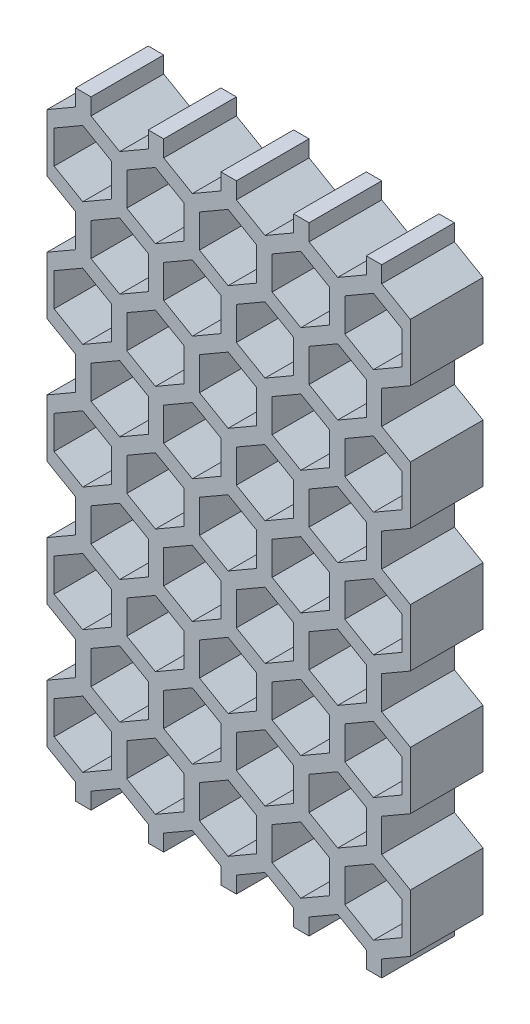
SolidWorks part; units mm, degrees
ref_plane "Front Plane" through (0, 0, 0) normal (0, 0, 1) x (1, 0, 0)
ref_plane "Top Plane" through (0, 0, 0) normal (0, 1, 0) x (1, 0, 0)
ref_plane "Right Plane" through (0, 0, 0) normal (1, 0, 0) x (0, 0, -1)
sketch "Sketch1" plane through (0, 0, 0) normal (0, 0, 1) x (1, 0, 0)
  line L0 (1.25, -1.0104) -> (0.25, -1.5877)
  line L1 (0, 1.1547) -> (-1, 0.5774)
  line L2 (-1, 0.5774) -> (-1, -0.5774)
  line L3 (-1, -0.5774) -> (0, -1.1547)
  line L4 (0, -1.1547) -> (1, -0.5774)
  line L5 (1, -0.5774) -> (1, 0.5774)
  line L6 (1, 0.5774) -> (0, 1.1547)
  line L7 (0.25, -1.5877) -> (0.25, -2.7424)
  line L8 (0.25, -2.7424) -> (1.25, -3.3198)
  line L9 (1.25, -3.3198) -> (2.25, -2.7424)
  line L10 (2.25, -2.7424) -> (2.25, -1.5877)
  line L11 (2.25, -1.5877) -> (1.25, -1.0104)
  line L12 (3.79, -1.0104) -> (2.79, -1.5877)
  line L13 (2.54, 1.1547) -> (1.54, 0.5774)
  line L14 (1.54, 0.5774) -> (1.54, -0.5774)
  line L15 (1.54, -0.5774) -> (2.54, -1.1547)
  line L16 (2.54, -1.1547) -> (3.54, -0.5774)
  line L17 (3.54, -0.5774) -> (3.54, 0.5774)
  line L18 (3.54, 0.5774) -> (2.54, 1.1547)
  line L19 (2.79, -1.5877) -> (2.79, -2.7424)
  line L20 (2.79, -2.7424) -> (3.79, -3.3198)
  line L21 (3.79, -3.3198) -> (4.79, -2.7424)
  line L22 (4.79, -2.7424) -> (4.79, -1.5877)
  line L23 (4.79, -1.5877) -> (3.79, -1.0104)
  line L24 (6.33, -1.0104) -> (5.33, -1.5877)
  line L25 (5.08, 1.1547) -> (4.08, 0.5774)
  line L26 (4.08, 0.5774) -> (4.08, -0.5774)
  line L27 (4.08, -0.5774) -> (5.08, -1.1547)
  line L28 (5.08, -1.1547) -> (6.08, -0.5774)
  line L29 (6.08, -0.5774) -> (6.08, 0.5774)
  line L30 (6.08, 0.5774) -> (5.08, 1.1547)
  line L31 (5.33, -1.5877) -> (5.33, -2.7424)
  line L32 (5.33, -2.7424) -> (6.33, -3.3198)
  line L33 (6.33, -3.3198) -> (7.33, -2.7424)
  line L34 (7.33, -2.7424) -> (7.33, -1.5877)
  line L35 (7.33, -1.5877) -> (6.33, -1.0104)
  line L36 (8.87, -1.0104) -> (7.87, -1.5877)
  line L37 (7.62, 1.1547) -> (6.62, 0.5774)
  line L38 (6.62, 0.5774) -> (6.62, -0.5774)
  line L39 (6.62, -0.5774) -> (7.62, -1.1547)
  line L40 (7.62, -1.1547) -> (8.62, -0.5774)
  line L41 (8.62, -0.5774) -> (8.62, 0.5774)
  line L42 (8.62, 0.5774) -> (7.62, 1.1547)
  line L43 (7.87, -1.5877) -> (7.87, -2.7424)
  line L44 (7.87, -2.7424) -> (8.87, -3.3198)
  line L45 (8.87, -3.3198) -> (9.87, -2.7424)
  line L46 (9.87, -2.7424) -> (9.87, -1.5877)
  line L47 (9.87, -1.5877) -> (8.87, -1.0104)
  line L48 (11.41, -1.0104) -> (10.41, -1.5877)
  line L49 (10.16, 1.1547) -> (9.16, 0.5774)
  line L50 (9.16, 0.5774) -> (9.16, -0.5774)
  line L51 (9.16, -0.5774) -> (10.16, -1.1547)
  line L52 (10.16, -1.1547) -> (11.16, -0.5774)
  line L53 (11.16, -0.5774) -> (11.16, 0.5774)
  line L54 (11.16, 0.5774) -> (10.16, 1.1547)
  line L55 (10.41, -1.5877) -> (10.41, -2.7424)
  line L56 (10.41, -2.7424) -> (11.41, -3.3198)
  line L57 (11.41, -3.3198) -> (12.41, -2.7424)
  line L58 (12.41, -2.7424) -> (12.41, -1.5877)
  line L59 (12.41, -1.5877) -> (11.41, -1.0104)
  line L60 (13.95, -1.0104) -> (12.95, -1.5877)
  line L61 (12.7, 1.1547) -> (11.7, 0.5774)
  line L62 (11.7, 0.5774) -> (11.7, -0.5774)
  line L63 (11.7, -0.5774) -> (12.7, -1.1547)
  line L64 (12.7, -1.1547) -> (13.7, -0.5774)
  line L65 (13.7, -0.5774) -> (13.7, 0.5774)
  line L66 (13.7, 0.5774) -> (12.7, 1.1547)
  line L67 (12.95, -1.5877) -> (12.95, -2.7424)
  line L68 (12.95, -2.7424) -> (13.95, -3.3198)
  line L69 (13.95, -3.3198) -> (14.95, -2.7424)
  line L70 (14.95, -2.7424) -> (14.95, -1.5877)
  line L71 (14.95, -1.5877) -> (13.95, -1.0104)
  line L72 (3.79, -5.3284) -> (2.79, -5.9057)
  line L73 (2.54, -3.1633) -> (1.54, -3.7406)
  line L74 (1.54, -3.7406) -> (1.54, -4.8954)
  line L75 (1.54, -4.8954) -> (2.54, -5.4727)
  line L76 (2.54, -5.4727) -> (3.54, -4.8954)
  line L77 (3.54, -4.8954) -> (3.54, -3.7406)
  line L78 (3.54, -3.7406) -> (2.54, -3.1633)
  line L79 (2.79, -5.9057) -> (2.79, -7.0604)
  line L80 (2.79, -7.0604) -> (3.79, -7.6378)
  line L81 (3.79, -7.6378) -> (4.79, -7.0604)
  line L82 (4.79, -7.0604) -> (4.79, -5.9057)
  line L83 (4.79, -5.9057) -> (3.79, -5.3284)
  line L84 (6.33, -5.3284) -> (5.33, -5.9057)
  line L85 (5.08, -3.1633) -> (4.08, -3.7406)
  line L86 (4.08, -3.7406) -> (4.08, -4.8954)
  line L87 (4.08, -4.8954) -> (5.08, -5.4727)
  line L88 (5.08, -5.4727) -> (6.08, -4.8954)
  line L89 (6.08, -4.8954) -> (6.08, -3.7406)
  line L90 (6.08, -3.7406) -> (5.08, -3.1633)
  line L91 (5.33, -5.9057) -> (5.33, -7.0604)
  line L92 (5.33, -7.0604) -> (6.33, -7.6378)
  line L93 (6.33, -7.6378) -> (7.33, -7.0604)
  line L94 (7.33, -7.0604) -> (7.33, -5.9057)
  line L95 (7.33, -5.9057) -> (6.33, -5.3284)
  line L96 (8.87, -5.3284) -> (7.87, -5.9057)
  line L97 (7.62, -3.1633) -> (6.62, -3.7406)
  line L98 (6.62, -3.7406) -> (6.62, -4.8954)
  line L99 (6.62, -4.8954) -> (7.62, -5.4727)
  line L100 (7.62, -5.4727) -> (8.62, -4.8954)
  line L101 (8.62, -4.8954) -> (8.62, -3.7406)
  line L102 (8.62, -3.7406) -> (7.62, -3.1633)
  line L103 (7.87, -5.9057) -> (7.87, -7.0604)
  line L104 (7.87, -7.0604) -> (8.87, -7.6378)
  line L105 (8.87, -7.6378) -> (9.87, -7.0604)
  line L106 (9.87, -7.0604) -> (9.87, -5.9057)
  line L107 (9.87, -5.9057) -> (8.87, -5.3284)
  line L108 (11.41, -5.3284) -> (10.41, -5.9057)
  line L109 (10.16, -3.1633) -> (9.16, -3.7406)
  line L110 (9.16, -3.7406) -> (9.16, -4.8954)
  line L111 (9.16, -4.8954) -> (10.16, -5.4727)
  line L112 (10.16, -5.4727) -> (11.16, -4.8954)
  line L113 (11.16, -4.8954) -> (11.16, -3.7406)
  line L114 (11.16, -3.7406) -> (10.16, -3.1633)
  line L115 (10.41, -5.9057) -> (10.41, -7.0604)
  line L116 (10.41, -7.0604) -> (11.41, -7.6378)
  line L117 (11.41, -7.6378) -> (12.41, -7.0604)
  line L118 (12.41, -7.0604) -> (12.41, -5.9057)
  line L119 (12.41, -5.9057) -> (11.41, -5.3284)
  line L120 (13.95, -5.3284) -> (12.95, -5.9057)
  line L121 (12.7, -3.1633) -> (11.7, -3.7406)
  line L122 (11.7, -3.7406) -> (11.7, -4.8954)
  line L123 (11.7, -4.8954) -> (12.7, -5.4727)
  line L124 (12.7, -5.4727) -> (13.7, -4.8954)
  line L125 (13.7, -4.8954) -> (13.7, -3.7406)
  line L126 (13.7, -3.7406) -> (12.7, -3.1633)
  line L127 (12.95, -5.9057) -> (12.95, -7.0604)
  line L128 (12.95, -7.0604) -> (13.95, -7.6378)
  line L129 (13.95, -7.6378) -> (14.95, -7.0604)
  line L130 (14.95, -7.0604) -> (14.95, -5.9057)
  line L131 (14.95, -5.9057) -> (13.95, -5.3284)
  line L132 (3.79, -9.6464) -> (2.79, -10.2237)
  line L133 (2.54, -7.4813) -> (1.54, -8.0586)
  line L134 (1.54, -8.0586) -> (1.54, -9.2134)
  line L135 (1.54, -9.2134) -> (2.54, -9.7907)
  line L136 (2.54, -9.7907) -> (3.54, -9.2134)
  line L137 (3.54, -9.2134) -> (3.54, -8.0586)
  line L138 (3.54, -8.0586) -> (2.54, -7.4813)
  line L139 (2.79, -10.2237) -> (2.79, -11.3784)
  line L140 (2.79, -11.3784) -> (3.79, -11.9558)
  line L141 (3.79, -11.9558) -> (4.79, -11.3784)
  line L142 (4.79, -11.3784) -> (4.79, -10.2237)
  line L143 (4.79, -10.2237) -> (3.79, -9.6464)
  line L144 (6.33, -9.6464) -> (5.33, -10.2237)
  line L145 (5.08, -7.4813) -> (4.08, -8.0586)
  line L146 (4.08, -8.0586) -> (4.08, -9.2134)
  line L147 (4.08, -9.2134) -> (5.08, -9.7907)
  line L148 (5.08, -9.7907) -> (6.08, -9.2134)
  line L149 (6.08, -9.2134) -> (6.08, -8.0586)
  line L150 (6.08, -8.0586) -> (5.08, -7.4813)
  line L151 (5.33, -10.2237) -> (5.33, -11.3784)
  line L152 (5.33, -11.3784) -> (6.33, -11.9558)
  line L153 (6.33, -11.9558) -> (7.33, -11.3784)
  line L154 (7.33, -11.3784) -> (7.33, -10.2237)
  line L155 (7.33, -10.2237) -> (6.33, -9.6464)
  line L156 (8.87, -9.6464) -> (7.87, -10.2237)
  line L157 (7.62, -7.4813) -> (6.62, -8.0586)
  line L158 (6.62, -8.0586) -> (6.62, -9.2134)
  line L159 (6.62, -9.2134) -> (7.62, -9.7907)
  line L160 (7.62, -9.7907) -> (8.62, -9.2134)
  line L161 (8.62, -9.2134) -> (8.62, -8.0586)
  line L162 (8.62, -8.0586) -> (7.62, -7.4813)
  line L163 (7.87, -10.2237) -> (7.87, -11.3784)
  line L164 (7.87, -11.3784) -> (8.87, -11.9558)
  line L165 (8.87, -11.9558) -> (9.87, -11.3784)
  line L166 (9.87, -11.3784) -> (9.87, -10.2237)
  line L167 (9.87, -10.2237) -> (8.87, -9.6464)
  line L168 (11.41, -9.6464) -> (10.41, -10.2237)
  line L169 (10.16, -7.4813) -> (9.16, -8.0586)
  line L170 (9.16, -8.0586) -> (9.16, -9.2134)
  line L171 (9.16, -9.2134) -> (10.16, -9.7907)
  line L172 (10.16, -9.7907) -> (11.16, -9.2134)
  line L173 (11.16, -9.2134) -> (11.16, -8.0586)
  line L174 (11.16, -8.0586) -> (10.16, -7.4813)
  line L175 (10.41, -10.2237) -> (10.41, -11.3784)
  line L176 (10.41, -11.3784) -> (11.41, -11.9558)
  line L177 (11.41, -11.9558) -> (12.41, -11.3784)
  line L178 (12.41, -11.3784) -> (12.41, -10.2237)
  line L179 (12.41, -10.2237) -> (11.41, -9.6464)
  line L180 (13.95, -9.6464) -> (12.95, -10.2237)
  line L181 (12.7, -7.4813) -> (11.7, -8.0586)
  line L182 (11.7, -8.0586) -> (11.7, -9.2134)
  line L183 (11.7, -9.2134) -> (12.7, -9.7907)
  line L184 (12.7, -9.7907) -> (13.7, -9.2134)
  line L185 (13.7, -9.2134) -> (13.7, -8.0586)
  line L186 (13.7, -8.0586) -> (12.7, -7.4813)
  line L187 (12.95, -10.2237) -> (12.95, -11.3784)
  line L188 (12.95, -11.3784) -> (13.95, -11.9558)
  line L189 (13.95, -11.9558) -> (14.95, -11.3784)
  line L190 (14.95, -11.3784) -> (14.95, -10.2237)
  line L191 (14.95, -10.2237) -> (13.95, -9.6464)
  line L192 (3.79, -13.9644) -> (2.79, -14.5417)
  line L193 (2.54, -11.7993) -> (1.54, -12.3766)
  line L194 (1.54, -12.3766) -> (1.54, -13.5314)
  line L195 (1.54, -13.5314) -> (2.54, -14.1087)
  line L196 (2.54, -14.1087) -> (3.54, -13.5314)
  line L197 (3.54, -13.5314) -> (3.54, -12.3766)
  line L198 (3.54, -12.3766) -> (2.54, -11.7993)
  line L199 (2.79, -14.5417) -> (2.79, -15.6964)
  line L200 (2.79, -15.6964) -> (3.79, -16.2738)
  line L201 (3.79, -16.2738) -> (4.79, -15.6964)
  line L202 (4.79, -15.6964) -> (4.79, -14.5417)
  line L203 (4.79, -14.5417) -> (3.79, -13.9644)
  line L204 (6.33, -13.9644) -> (5.33, -14.5417)
  line L205 (5.08, -11.7993) -> (4.08, -12.3766)
  line L206 (4.08, -12.3766) -> (4.08, -13.5314)
  line L207 (4.08, -13.5314) -> (5.08, -14.1087)
  line L208 (5.08, -14.1087) -> (6.08, -13.5314)
  line L209 (6.08, -13.5314) -> (6.08, -12.3766)
  line L210 (6.08, -12.3766) -> (5.08, -11.7993)
  line L211 (5.33, -14.5417) -> (5.33, -15.6964)
  line L212 (5.33, -15.6964) -> (6.33, -16.2738)
  line L213 (6.33, -16.2738) -> (7.33, -15.6964)
  line L214 (7.33, -15.6964) -> (7.33, -14.5417)
  line L215 (7.33, -14.5417) -> (6.33, -13.9644)
  line L216 (8.87, -13.9644) -> (7.87, -14.5417)
  line L217 (7.62, -11.7993) -> (6.62, -12.3766)
  line L218 (6.62, -12.3766) -> (6.62, -13.5314)
  line L219 (6.62, -13.5314) -> (7.62, -14.1087)
  line L220 (7.62, -14.1087) -> (8.62, -13.5314)
  line L221 (8.62, -13.5314) -> (8.62, -12.3766)
  line L222 (8.62, -12.3766) -> (7.62, -11.7993)
  line L223 (7.87, -14.5417) -> (7.87, -15.6964)
  line L224 (7.87, -15.6964) -> (8.87, -16.2738)
  line L225 (8.87, -16.2738) -> (9.87, -15.6964)
  line L226 (9.87, -15.6964) -> (9.87, -14.5417)
  line L227 (9.87, -14.5417) -> (8.87, -13.9644)
  line L228 (11.41, -13.9644) -> (10.41, -14.5417)
  line L229 (10.16, -11.7993) -> (9.16, -12.3766)
  line L230 (9.16, -12.3766) -> (9.16, -13.5314)
  line L231 (9.16, -13.5314) -> (10.16, -14.1087)
  line L232 (10.16, -14.1087) -> (11.16, -13.5314)
  line L233 (11.16, -13.5314) -> (11.16, -12.3766)
  line L234 (11.16, -12.3766) -> (10.16, -11.7993)
  line L235 (10.41, -14.5417) -> (10.41, -15.6964)
  line L236 (10.41, -15.6964) -> (11.41, -16.2738)
  line L237 (11.41, -16.2738) -> (12.41, -15.6964)
  line L238 (12.41, -15.6964) -> (12.41, -14.5417)
  line L239 (12.41, -14.5417) -> (11.41, -13.9644)
  line L240 (13.95, -13.9644) -> (12.95, -14.5417)
  line L241 (12.7, -11.7993) -> (11.7, -12.3766)
  line L242 (11.7, -12.3766) -> (11.7, -13.5314)
  line L243 (11.7, -13.5314) -> (12.7, -14.1087)
  line L244 (12.7, -14.1087) -> (13.7, -13.5314)
  line L245 (13.7, -13.5314) -> (13.7, -12.3766)
  line L246 (13.7, -12.3766) -> (12.7, -11.7993)
  line L247 (12.95, -14.5417) -> (12.95, -15.6964)
  line L248 (12.95, -15.6964) -> (13.95, -16.2738)
  line L249 (13.95, -16.2738) -> (14.95, -15.6964)
  line L250 (14.95, -15.6964) -> (14.95, -14.5417)
  line L251 (14.95, -14.5417) -> (13.95, -13.9644)
  line L252 (3.79, -18.2824) -> (2.79, -18.8597)
  line L253 (2.54, -16.1173) -> (1.54, -16.6946)
  line L254 (1.54, -16.6946) -> (1.54, -17.8494)
  line L255 (1.54, -17.8494) -> (2.54, -18.4267)
  line L256 (2.54, -18.4267) -> (3.54, -17.8494)
  line L257 (3.54, -17.8494) -> (3.54, -16.6946)
  line L258 (3.54, -16.6946) -> (2.54, -16.1173)
  line L259 (2.79, -18.8597) -> (2.79, -20.0144)
  line L260 (2.79, -20.0144) -> (3.79, -20.5918)
  line L261 (3.79, -20.5918) -> (4.79, -20.0144)
  line L262 (4.79, -20.0144) -> (4.79, -18.8597)
  line L263 (4.79, -18.8597) -> (3.79, -18.2824)
  line L264 (6.33, -18.2824) -> (5.33, -18.8597)
  line L265 (5.08, -16.1173) -> (4.08, -16.6946)
  line L266 (4.08, -16.6946) -> (4.08, -17.8494)
  line L267 (4.08, -17.8494) -> (5.08, -18.4267)
  line L268 (5.08, -18.4267) -> (6.08, -17.8494)
  line L269 (6.08, -17.8494) -> (6.08, -16.6946)
  line L270 (6.08, -16.6946) -> (5.08, -16.1173)
  line L271 (5.33, -18.8597) -> (5.33, -20.0144)
  line L272 (5.33, -20.0144) -> (6.33, -20.5918)
  line L273 (6.33, -20.5918) -> (7.33, -20.0144)
  line L274 (7.33, -20.0144) -> (7.33, -18.8597)
  line L275 (7.33, -18.8597) -> (6.33, -18.2824)
  line L276 (8.87, -18.2824) -> (7.87, -18.8597)
  line L277 (7.62, -16.1173) -> (6.62, -16.6946)
  line L278 (6.62, -16.6946) -> (6.62, -17.8494)
  line L279 (6.62, -17.8494) -> (7.62, -18.4267)
  line L280 (7.62, -18.4267) -> (8.62, -17.8494)
  line L281 (8.62, -17.8494) -> (8.62, -16.6946)
  line L282 (8.62, -16.6946) -> (7.62, -16.1173)
  line L283 (7.87, -18.8597) -> (7.87, -20.0144)
  line L284 (7.87, -20.0144) -> (8.87, -20.5918)
  line L285 (8.87, -20.5918) -> (9.87, -20.0144)
  line L286 (9.87, -20.0144) -> (9.87, -18.8597)
  line L287 (9.87, -18.8597) -> (8.87, -18.2824)
  line L288 (11.41, -18.2824) -> (10.41, -18.8597)
  line L289 (10.16, -16.1173) -> (9.16, -16.6946)
  line L290 (9.16, -16.6946) -> (9.16, -17.8494)
  line L291 (9.16, -17.8494) -> (10.16, -18.4267)
  line L292 (10.16, -18.4267) -> (11.16, -17.8494)
  line L293 (11.16, -17.8494) -> (11.16, -16.6946)
  line L294 (11.16, -16.6946) -> (10.16, -16.1173)
  line L295 (10.41, -18.8597) -> (10.41, -20.0144)
  line L296 (10.41, -20.0144) -> (11.41, -20.5918)
  line L297 (11.41, -20.5918) -> (12.41, -20.0144)
  line L298 (12.41, -20.0144) -> (12.41, -18.8597)
  line L299 (12.41, -18.8597) -> (11.41, -18.2824)
  line L300 (13.95, -18.2824) -> (12.95, -18.8597)
  line L301 (12.7, -16.1173) -> (11.7, -16.6946)
  line L302 (11.7, -16.6946) -> (11.7, -17.8494)
  line L303 (11.7, -17.8494) -> (12.7, -18.4267)
  line L304 (12.7, -18.4267) -> (13.7, -17.8494)
  line L305 (13.7, -17.8494) -> (13.7, -16.6946)
  line L306 (13.7, -16.6946) -> (12.7, -16.1173)
  line L307 (12.95, -18.8597) -> (12.95, -20.0144)
  line L308 (12.95, -20.0144) -> (13.95, -20.5918)
  line L309 (13.95, -20.5918) -> (14.95, -20.0144)
  line L310 (14.95, -20.0144) -> (14.95, -18.8597)
  line L311 (14.95, -18.8597) -> (13.95, -18.2824)
  line L312 (3.79, -22.6004) -> (2.79, -23.1777)
  line L313 (2.54, -20.4353) -> (1.54, -21.0126)
  line L314 (1.54, -21.0126) -> (1.54, -22.1674)
  line L315 (1.54, -22.1674) -> (2.54, -22.7447)
  line L316 (2.54, -22.7447) -> (3.54, -22.1674)
  line L317 (3.54, -22.1674) -> (3.54, -21.0126)
  line L318 (3.54, -21.0126) -> (2.54, -20.4353)
  line L319 (2.79, -23.1777) -> (2.79, -24.3324)
  line L320 (2.79, -24.3324) -> (3.79, -24.9098)
  line L321 (3.79, -24.9098) -> (4.79, -24.3324)
  line L322 (4.79, -24.3324) -> (4.79, -23.1777)
  line L323 (4.79, -23.1777) -> (3.79, -22.6004)
  line L324 (6.33, -22.6004) -> (5.33, -23.1777)
  line L325 (5.08, -20.4353) -> (4.08, -21.0126)
  line L326 (4.08, -21.0126) -> (4.08, -22.1674)
  line L327 (4.08, -22.1674) -> (5.08, -22.7447)
  line L328 (5.08, -22.7447) -> (6.08, -22.1674)
  line L329 (6.08, -22.1674) -> (6.08, -21.0126)
  line L330 (6.08, -21.0126) -> (5.08, -20.4353)
  line L331 (5.33, -23.1777) -> (5.33, -24.3324)
  line L332 (5.33, -24.3324) -> (6.33, -24.9098)
  line L333 (6.33, -24.9098) -> (7.33, -24.3324)
  line L334 (7.33, -24.3324) -> (7.33, -23.1777)
  line L335 (7.33, -23.1777) -> (6.33, -22.6004)
  line L336 (8.87, -22.6004) -> (7.87, -23.1777)
  line L337 (7.62, -20.4353) -> (6.62, -21.0126)
  line L338 (6.62, -21.0126) -> (6.62, -22.1674)
  line L339 (6.62, -22.1674) -> (7.62, -22.7447)
  line L340 (7.62, -22.7447) -> (8.62, -22.1674)
  line L341 (8.62, -22.1674) -> (8.62, -21.0126)
  line L342 (8.62, -21.0126) -> (7.62, -20.4353)
  line L343 (7.87, -23.1777) -> (7.87, -24.3324)
  line L344 (7.87, -24.3324) -> (8.87, -24.9098)
  line L345 (8.87, -24.9098) -> (9.87, -24.3324)
  line L346 (9.87, -24.3324) -> (9.87, -23.1777)
  line L347 (9.87, -23.1777) -> (8.87, -22.6004)
  line L348 (11.41, -22.6004) -> (10.41, -23.1777)
  line L349 (10.16, -20.4353) -> (9.16, -21.0126)
  line L350 (9.16, -21.0126) -> (9.16, -22.1674)
  line L351 (9.16, -22.1674) -> (10.16, -22.7447)
  line L352 (10.16, -22.7447) -> (11.16, -22.1674)
  line L353 (11.16, -22.1674) -> (11.16, -21.0126)
  line L354 (11.16, -21.0126) -> (10.16, -20.4353)
  line L355 (10.41, -23.1777) -> (10.41, -24.3324)
  line L356 (10.41, -24.3324) -> (11.41, -24.9098)
  line L357 (11.41, -24.9098) -> (12.41, -24.3324)
  line L358 (12.41, -24.3324) -> (12.41, -23.1777)
  line L359 (12.41, -23.1777) -> (11.41, -22.6004)
  line L360 (13.95, -22.6004) -> (12.95, -23.1777)
  line L361 (12.7, -20.4353) -> (11.7, -21.0126)
  line L362 (11.7, -21.0126) -> (11.7, -22.1674)
  line L363 (11.7, -22.1674) -> (12.7, -22.7447)
  line L364 (12.7, -22.7447) -> (13.7, -22.1674)
  line L365 (13.7, -22.1674) -> (13.7, -21.0126)
  line L366 (13.7, -21.0126) -> (12.7, -20.4353)
  line L367 (12.95, -23.1777) -> (12.95, -24.3324)
  line L368 (12.95, -24.3324) -> (13.95, -24.9098)
  line L369 (13.95, -24.9098) -> (14.95, -24.3324)
  line L370 (14.95, -24.3324) -> (14.95, -23.1777)
  line L371 (14.95, -23.1777) -> (13.95, -22.6004)
  line L372 (1.25, -5.3284) -> (0.25, -5.9057)
  line L373 (0, -3.1633) -> (-1, -3.7406)
  line L374 (-1, -3.7406) -> (-1, -4.8954)
  line L375 (-1, -4.8954) -> (0, -5.4727)
  line L376 (0, -5.4727) -> (1, -4.8954)
  line L377 (1, -4.8954) -> (1, -3.7406)
  line L378 (1, -3.7406) -> (0, -3.1633)
  line L379 (0.25, -5.9057) -> (0.25, -7.0604)
  line L380 (0.25, -7.0604) -> (1.25, -7.6378)
  line L381 (1.25, -7.6378) -> (2.25, -7.0604)
  line L382 (2.25, -7.0604) -> (2.25, -5.9057)
  line L383 (2.25, -5.9057) -> (1.25, -5.3284)
  line L384 (1.25, -9.6464) -> (0.25, -10.2237)
  line L385 (0, -7.4813) -> (-1, -8.0586)
  line L386 (-1, -8.0586) -> (-1, -9.2134)
  line L387 (-1, -9.2134) -> (0, -9.7907)
  line L388 (0, -9.7907) -> (1, -9.2134)
  line L389 (1, -9.2134) -> (1, -8.0586)
  line L390 (1, -8.0586) -> (0, -7.4813)
  line L391 (0.25, -10.2237) -> (0.25, -11.3784)
  line L392 (0.25, -11.3784) -> (1.25, -11.9558)
  line L393 (1.25, -11.9558) -> (2.25, -11.3784)
  line L394 (2.25, -11.3784) -> (2.25, -10.2237)
  line L395 (2.25, -10.2237) -> (1.25, -9.6464)
  line L396 (1.25, -13.9644) -> (0.25, -14.5417)
  line L397 (0, -11.7993) -> (-1, -12.3766)
  line L398 (-1, -12.3766) -> (-1, -13.5314)
  line L399 (-1, -13.5314) -> (0, -14.1087)
  line L400 (0, -14.1087) -> (1, -13.5314)
  line L401 (1, -13.5314) -> (1, -12.3766)
  line L402 (1, -12.3766) -> (0, -11.7993)
  line L403 (0.25, -14.5417) -> (0.25, -15.6964)
  line L404 (0.25, -15.6964) -> (1.25, -16.2738)
  line L405 (1.25, -16.2738) -> (2.25, -15.6964)
  line L406 (2.25, -15.6964) -> (2.25, -14.5417)
  line L407 (2.25, -14.5417) -> (1.25, -13.9644)
  line L408 (1.25, -18.2824) -> (0.25, -18.8597)
  line L409 (0, -16.1173) -> (-1, -16.6946)
  line L410 (-1, -16.6946) -> (-1, -17.8494)
  line L411 (-1, -17.8494) -> (0, -18.4267)
  line L412 (0, -18.4267) -> (1, -17.8494)
  line L413 (1, -17.8494) -> (1, -16.6946)
  line L414 (1, -16.6946) -> (0, -16.1173)
  line L415 (0.25, -18.8597) -> (0.25, -20.0144)
  line L416 (0.25, -20.0144) -> (1.25, -20.5918)
  line L417 (1.25, -20.5918) -> (2.25, -20.0144)
  line L418 (2.25, -20.0144) -> (2.25, -18.8597)
  line L419 (2.25, -18.8597) -> (1.25, -18.2824)
  line L420 (1.25, -22.6004) -> (0.25, -23.1777)
  line L421 (0, -20.4353) -> (-1, -21.0126)
  line L422 (-1, -21.0126) -> (-1, -22.1674)
  line L423 (-1, -22.1674) -> (0, -22.7447)
  line L424 (0, -22.7447) -> (1, -22.1674)
  line L425 (1, -22.1674) -> (1, -21.0126)
  line L426 (1, -21.0126) -> (0, -20.4353)
  line L427 (0.25, -23.1777) -> (0.25, -24.3324)
  line L428 (0.25, -24.3324) -> (1.25, -24.9098)
  line L429 (1.25, -24.9098) -> (2.25, -24.3324)
  line L430 (2.25, -24.3324) -> (2.25, -23.1777)
  line L431 (2.25, -23.1777) -> (1.25, -22.6004)
  line L433 (0, 0) -> (12.7, 0)
  line L434 (0, 0) -> (0, -21.59)
  line L435 (0, -21.59) -> (12.7, -21.59)
  line L436 (12.7, 0) -> (12.7, -21.59)
  circle A0 centre (0, 0) radius 1 construction
  circle A1 centre (2.54, 0) radius 1 construction
  circle A2 centre (5.08, 0) radius 1 construction
  circle A3 centre (7.62, 0) radius 1 construction
  circle A4 centre (10.16, 0) radius 1 construction
  circle A5 centre (12.7, 0) radius 1 construction
  circle A6 centre (2.54, -4.318) radius 1 construction
  circle A7 centre (5.08, -4.318) radius 1 construction
  circle A8 centre (7.62, -4.318) radius 1 construction
  circle A9 centre (10.16, -4.318) radius 1 construction
  circle A10 centre (12.7, -4.318) radius 1 construction
  circle A11 centre (2.54, -8.636) radius 1 construction
  circle A12 centre (5.08, -8.636) radius 1 construction
  circle A13 centre (7.62, -8.636) radius 1 construction
  circle A14 centre (10.16, -8.636) radius 1 construction
  circle A15 centre (12.7, -8.636) radius 1 construction
  circle A16 centre (2.54, -12.954) radius 1 construction
  circle A17 centre (5.08, -12.954) radius 1 construction
  circle A18 centre (7.62, -12.954) radius 1 construction
  circle A19 centre (10.16, -12.954) radius 1 construction
  circle A20 centre (12.7, -12.954) radius 1 construction
  circle A21 centre (2.54, -17.272) radius 1 construction
  circle A22 centre (5.08, -17.272) radius 1 construction
  circle A23 centre (7.62, -17.272) radius 1 construction
  circle A24 centre (10.16, -17.272) radius 1 construction
  circle A25 centre (12.7, -17.272) radius 1 construction
  circle A26 centre (2.54, -21.59) radius 1 construction
  circle A27 centre (5.08, -21.59) radius 1 construction
  circle A28 centre (7.62, -21.59) radius 1 construction
  circle A29 centre (10.16, -21.59) radius 1 construction
  circle A30 centre (12.7, -21.59) radius 1 construction
  circle A31 centre (0, -4.318) radius 1 construction
  circle A32 centre (0, -8.636) radius 1 construction
  circle A33 centre (0, -12.954) radius 1 construction
  circle A34 centre (0, -17.272) radius 1 construction
  circle A35 centre (0, -21.59) radius 1 construction
  dimension "D1" = 2
  dimension "D2" = 2
  dimension "D3" = 0.5
  dimension "D4" = 0.25
  dimension "D5" = 2
  dimension "D6" = 2.25
  dimension "D7" = 3.8971
  dimension "D8" = 0.433
  dimension "D9" = 6
  dimension "D10" = 6
extrude "Boss-Extrude1" add sketch "Sketch1" along normal mid plane 2.54 contours L436 L63 L62 L433 L53 L52 L51 L50 L41 L40 L39 L38 L29 L28 L27 L26 L17 L16 L15 L14 L5 L4 L434 L378 L377 L376 L390 L389 L388 L402 L401 L400 L414 L413 L412 L426 L425 L435 L314 L313 L318 L317 region at (1.27, -0.2505, 0)
